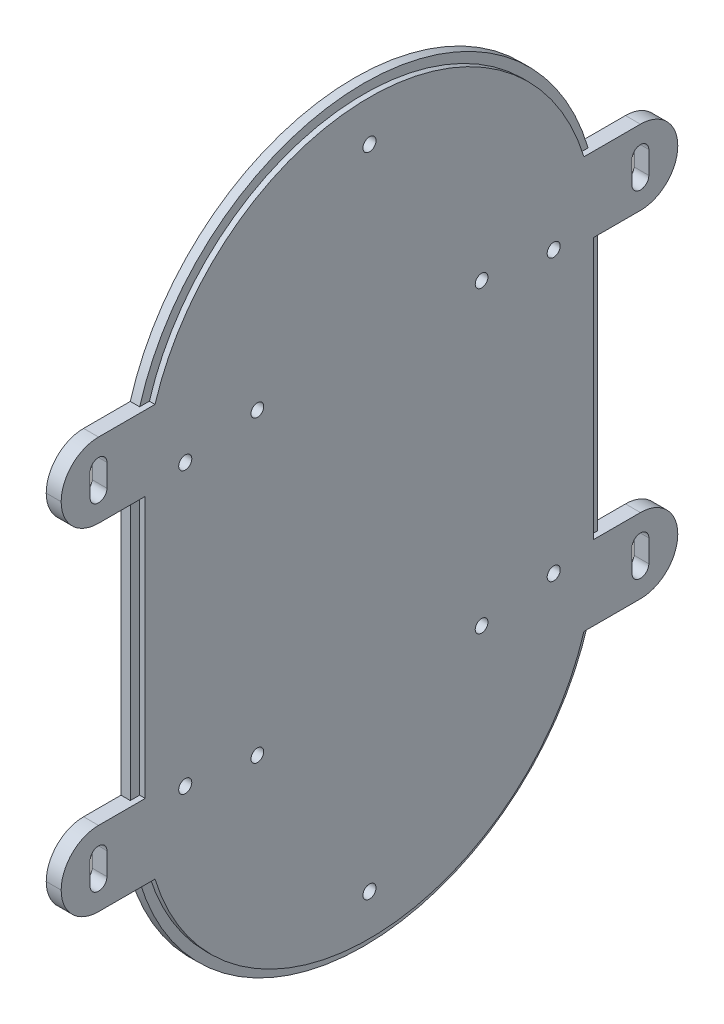
SolidWorks part; units mm, degrees
other "Markup1"
sketch "Sketch8" plane through (4, 100, -82.5) normal (0.9895, 0.0002, -0.1449) x (-0.1441, -0.0996, -0.9845)
ref_plane "Front Plane" through (0, 0, 0) normal (0, 0, 1) x (1, 0, 0)
ref_plane "Top Plane" through (0, 0, 0) normal (0, 1, 0) x (1, 0, 0)
ref_plane "Right Plane" through (0, 0, 0) normal (1, 0, 0) x (0, 0, -1)
sketch "Sketch1" plane through (0, 0, 0) normal (1, 0, 0) x (0, 0, -1)
  line L0 (0, 100) -> (0, 37.5) construction
  line L2 (-62.5, -37.5) -> (-62.5, 37.5)
  line L4 (62.5, -37.5) -> (62.5, 37.5)
  line L7 (0, 0) -> (62.5, 0) construction
  line L8 (0, 0) -> (0, -100) construction
  arc A0 (62.5, 37.5) -> (-62.5, 37.5) centre (0, 37.5) ccw
  arc A1 (62.5, -37.5) -> (-62.5, -37.5) centre (0, -37.5) cw
  point P0 (0, 0)
  dimension "D1" = 75
  dimension "D2" = 62.5
  dimension "D3" = 62.5
  dimension "D4" = 125
extrude "Boss-Extrude1" add sketch "Sketch1" along normal blind 2.5
sketch "Sketch2" plane through (2.5, 0, 0) normal (1, 0, 0) x (0, 0, -1)
  line L2 (-62.5, 37.5) -> (-62.5, -37.5)
  line L3 (62.5, -37.5) -> (62.5, 37.5)
  line L4 (-62.5, 37.5) -> (-62.5, -37.5) construction
  line L5 (62.5, -37.5) -> (62.5, 37.5) construction
  line L8 (-60, 37.5) -> (-60, -37.5)
  line L9 (60, -37.5) -> (60, 37.5)
  line L10 (-60, 37.5) -> (-60, -37.5)
  line L11 (60, -37.5) -> (60, 37.5)
  arc A2 (62.5, 37.5) -> (-62.5, 37.5) centre (0, 37.5) ccw
  arc A3 (-62.5, -37.5) -> (62.5, -37.5) centre (0, -37.5) ccw
  arc A4 (62.5, 37.5) -> (-62.5, 37.5) centre (0, 37.5) ccw construction
  arc A5 (-62.5, -37.5) -> (62.5, -37.5) centre (0, -37.5) ccw construction
  arc A8 (60, 37.5) -> (-60, 37.5) centre (0, 37.5) ccw
  arc A9 (-60, -37.5) -> (60, -37.5) centre (0, -37.5) ccw
  arc A10 (60, 37.5) -> (-60, 37.5) centre (0, 37.5) ccw
  arc A11 (-60, -37.5) -> (60, -37.5) centre (0, -37.5) ccw
  dimension "D1" = 0
  dimension "D2" = 2.5
extrude "Boss-Extrude2" add sketch "Sketch2" along normal blind 1.5
ref_plane "Plane1" through (0, 0, -82.5) normal (0, 0, -1) x (-1, 0, 0)
sketch "Sketch4" plane through (0, 0, -82.5) normal (0, 0, -1) x (-1, 0, 0)
  line L0 (0, 0) -> (0, 100) construction
  line L1 (0, 37.5) -> (0, 100) construction
  line L2 (0, 0) -> (-4, 0) construction
  line L3 (-4, -37.5) -> (-4, 37.5) construction
  line L4 (-4, 97.5) -> (-4, 37.5) construction
  line L5 (0, 35) -> (-4, 35)
  line L6 (0, 35) -> (0, 55)
  line L7 (0, 55) -> (-4, 55)
  line L8 (-4, 35) -> (-4, 55)
  line L9 (0, -55) -> (-4, -55)
  line L10 (-4, -35) -> (-4, -55)
  line L11 (0, -35) -> (-4, -35)
  line L12 (0, -35) -> (0, -55)
  dimension "D1" = 100
  dimension "D2" = 20
  dimension "D3" = 35
extrude "Boss-Extrude3" add sketch "Sketch4" against normal up to next
ref_plane "Plane2" through (0, 0, 0) normal (0, 0, -1) x (-1, 0, 0)
fillet "Fillet1" radius 10 4 edges at (2, -55, -82.5) (2, -35, -82.5) (2, 35, -82.5) (2, 55, -82.5)
sketch "Sketch5" plane through (4, 0, 0) normal (1, 0, 0) x (0, 0, -1)
  line L0 (82.5, 45) -> (0, 45) construction
  line L1 (72.5, 42) -> (72.5, 48) construction
  line L2 (70.25, 42) -> (70.25, 48)
  line L3 (74.75, 42) -> (74.75, 48)
  line L4 (82.5, -45) -> (72.5, -45) construction
  line L5 (72.5, -48) -> (72.5, -42) construction
  line L6 (70.25, -48) -> (70.25, -42)
  line L7 (74.75, -48) -> (74.75, -42)
  arc A2 (70.25, 42) -> (74.75, 42) centre (72.5, 42) ccw
  arc A3 (74.75, 48) -> (70.25, 48) centre (72.5, 48) ccw
  arc A4 (70.25, -48) -> (74.75, -48) centre (72.5, -48) ccw
  arc A5 (74.75, -42) -> (70.25, -42) centre (72.5, -42) ccw
  point P8 (72.5, 45)
  point P19 (72.5, -45)
  dimension "D1" = 6
  dimension "D2" = 2.25
  dimension "D5" = 2.25
  dimension "D3" = 10
  dimension "D4" = 6
mirror "Mirror2" about plane through (0, 0, 0) normal (0, 0, -1) of "Fillet1", "Boss-Extrude3"
sketch "Sketch6" plane through (4, 0, 0) normal (1, 0, 0) x (0, 0, -1)
  line L0 (-35, 0) -> (-60, 0) construction
  line L1 (-35, -45) -> (35, -45) construction
  line L2 (-35, -45) -> (-35, 45) construction
  line L3 (-35, 45) -> (35, 45) construction
  line L4 (35, -45) -> (35, 45) construction
  line L5 (-35, -45) -> (35, 45) construction
  line L6 (-35, 45) -> (35, -45) construction
  line L7 (-60, 35) -> (-60, -35) construction
  line L8 (0, 0) -> (0, 45) construction
  line L9 (0, 0) -> (35, 0) construction
  circle A0 centre (-30, 40) radius 1.5 construction
  circle A2 centre (-30, 40) radius 1.7
  circle A3 centre (30, 40) radius 1.7
  circle A4 centre (30, -40) radius 1.7
  circle A5 centre (-30, -40) radius 1.7
  point P0 (0, 0)
  dimension "D4" = 3
  dimension "D5" = 5
  dimension "D6" = 5
  dimension "D7" = 3.4
  dimension "D1" = 70
  dimension "D2" = 90
  dimension "D3" = 25
extrude "Cut-Extrude2" cut sketch "Sketch6" against normal through all
sketch "Sketch7" plane through (4, 0, 0) normal (1, 0, 0) x (0, 0, -1)
  line L0 (0, 100) -> (0, -100) construction
  line L1 (0, 86.58) -> (0, 37.5) construction
  line L2 (0, 37.5) -> (49.3, 37.5) construction
  line L3 (0, 0) -> (62.5, 0) construction
  line L4 (62.5, -35) -> (62.5, 35) construction
  arc A0 (60, 55) -> (-60, 55) centre (0, 37.5) ccw construction
  arc A1 (-60, -55) -> (60, -55) centre (0, -37.5) ccw construction
  circle A2 centre (0, 86.58) radius 1.75
  circle A3 centre (49.3, 37.5) radius 1.75
  circle A4 centre (-49.3, 37.5) radius 1.75
  circle A5 centre (49.3, -37.5) radius 1.75
  circle A6 centre (0, -86.58) radius 1.75
  circle A7 centre (-49.3, -37.5) radius 1.75
  dimension "D1" = 3.5
  dimension "D5" = 3.5
  dimension "D2" = 13.42
  dimension "D3" = 49.08
  dimension "D4" = 49.3
extrude "Cut-Extrude3" cut sketch "Sketch7" against normal through all
extrude "Cut-Extrude4" cut sketch "Sketch5" against normal through all
mirror "Mirror3" about plane through (0, 0, 0) normal (0, 0, -1) of "Cut-Extrude4"
